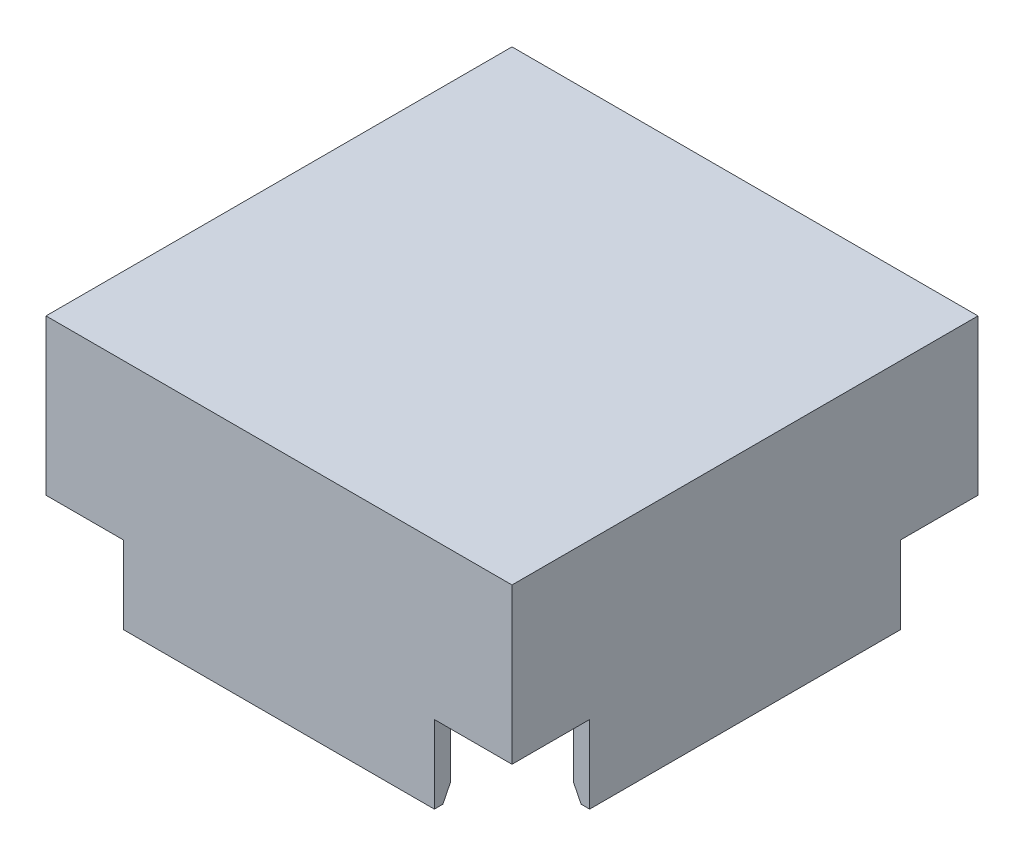
SolidWorks part; units mm, degrees
ref_plane "Front Plane" through (0, 0, 0) normal (0, 0, 1) x (1, 0, 0)
ref_plane "Top Plane" through (0, 0, 0) normal (0, 1, 0) x (1, 0, 0)
ref_plane "Right Plane" through (0, 0, 0) normal (1, 0, 0) x (0, 0, -1)
sketch "Sketch1" plane through (0, 1478.6171, 0) normal (0, 1, 0) x (1, 0, 0)
  line L1 (-530.1492, -768.8296) -> (-453.9492, -768.8296)
  line L2 (-530.1492, -768.8296) -> (-530.1492, -845.0296)
  line L3 (-530.1492, -845.0296) -> (-453.9492, -845.0296)
  line L4 (-453.9492, -768.8296) -> (-453.9492, -845.0296)
  line L5 (-530.1492, -768.8296) -> (-453.9492, -845.0296) construction
  line L6 (-530.1492, -845.0296) -> (-453.9492, -768.8296) construction
  point P0 (-492.0492, -806.9296)
  dimension "D1" = 76.2
  dimension "D2" = 76.2
extrude "Boss-Extrude1" add sketch "Sketch1" along normal blind 25.4
sketch "Sketch2" plane through (0, 1478.6171, 0) normal (0, -1, 0) x (-1, 0, 0)
  line L1 (463.4742, -778.3546) -> (520.6242, -778.3546)
  line L2 (463.4742, -778.3546) -> (463.4742, -835.5046)
  line L3 (463.4742, -835.5046) -> (520.6242, -835.5046)
  line L4 (520.6242, -778.3546) -> (520.6242, -835.5046)
  line L5 (463.4742, -778.3546) -> (520.6242, -835.5046) construction
  line L6 (463.4742, -835.5046) -> (520.6242, -778.3546) construction
  point P0 (492.0492, -806.9296)
  dimension "D1" = 57.15
  dimension "D2" = 57.15
extrude "Cut-Extrude1" cut sketch "Sketch2" against normal blind 19.05
sketch "Sketch3" plane through (0, 1478.6171, 0) normal (0, -1, 0) x (-1, 0, 0)
  line L0 (530.1492, -768.8296) -> (530.1492, -845.0296) construction
  line L1 (530.1492, -781.5296) -> (527.4822, -781.5296)
  line L2 (530.1492, -781.5296) -> (530.1492, -832.3296)
  line L3 (530.1492, -832.3296) -> (527.4822, -832.3296)
  line L4 (527.4822, -781.5296) -> (527.4822, -832.3296)
  line L5 (453.9492, -768.8296) -> (530.1492, -768.8296) construction
  line L6 (517.4492, -768.8296) -> (466.6492, -768.8296)
  line L7 (517.4492, -768.8296) -> (517.4492, -771.4966)
  line L8 (517.4492, -771.4966) -> (466.6492, -771.4966)
  line L9 (466.6492, -768.8296) -> (466.6492, -771.4966)
  line L10 (530.1492, -845.0296) -> (453.9492, -845.0296) construction
  line L11 (517.4492, -845.0296) -> (466.6492, -845.0296)
  line L12 (517.4492, -845.0296) -> (517.4492, -842.3626)
  line L13 (517.4492, -842.3626) -> (466.6492, -842.3626)
  line L14 (466.6492, -845.0296) -> (466.6492, -842.3626)
  line L15 (453.9492, -845.0296) -> (453.9492, -768.8296) construction
  line L16 (453.9492, -832.3296) -> (456.6162, -832.3296)
  line L17 (453.9492, -832.3296) -> (453.9492, -781.5296)
  line L18 (453.9492, -781.5296) -> (456.6162, -781.5296)
  line L19 (456.6162, -832.3296) -> (456.6162, -781.5296)
  line L20 (457.1242, -772.0046) -> (457.1242, -841.8546) construction
  line L21 (457.1242, -841.8546) -> (526.9742, -841.8546) construction
  line L22 (526.9742, -772.0046) -> (457.1242, -772.0046) construction
  line L23 (526.9742, -841.8546) -> (526.9742, -772.0046) construction
  dimension "D1" = 12.7
  dimension "D2" = 12.7
  dimension "D3" = 12.7
  dimension "D4" = 12.7
  dimension "D5" = 12.7
  dimension "D6" = 12.7
  dimension "D7" = 12.7
  dimension "D8" = 12.7
  dimension "D9" = 0.508
  dimension "D10" = 0.508
  dimension "D11" = 0.508
  dimension "D12" = 0.508
extrude "Boss-Extrude2" add sketch "Sketch3" along normal blind 12.7
chamfer "Chamfer1" distance 2.54 distance2 1.27 4 edges at (-492.0492, 1465.9171, 842.3626) (-527.4822, 1465.9171, 806.9296) (-456.6162, 1465.9171, 806.9296) (-492.0492, 1465.9171, 771.4966) first distance on face at (-492.0492, 1472.2671, 842.3626) first distance on face at (-527.4822, 1472.2671, 806.9296) first distance on face at (-456.6162, 1472.2671, 806.9296) first distance on face at (-492.0492, 1472.2671, 771.4966)
